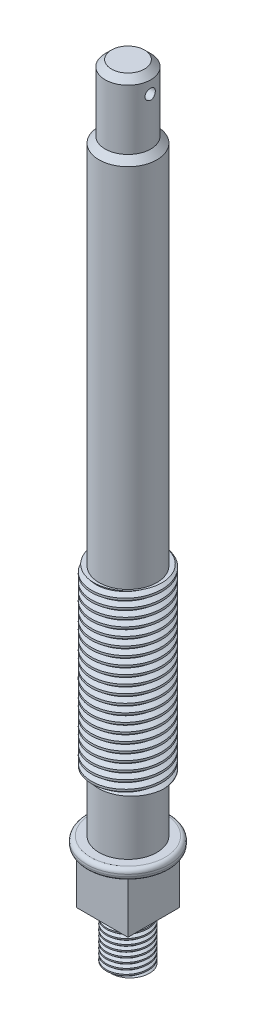
SolidWorks part; units mm, degrees
ref_plane "Front Plane" through (0, 0, 0) normal (0, 0, 1) x (1, 0, 0)
ref_plane "Top Plane" through (0, 0, 0) normal (0, 1, 0) x (1, 0, 0)
ref_plane "Right Plane" through (0, 0, 0) normal (1, 0, 0) x (0, 0, -1)
sketch "Sketch1" plane through (0, 0, 0) normal (0, 0, 1) x (1, 0, 0)
  line L0 (0, -0.1214) -> (0, -30394.4692) construction
  line L1 (0, 0) -> (30394.3478, 0) construction
  line L2 (0, 0) -> (11, 0)
  line L3 (11, 0) -> (11, -32)
  line L4 (11, -32) -> (14, -32)
  line L5 (14, -32) -> (14, -212)
  line L6 (14, -212) -> (17, -212)
  line L7 (17, -212) -> (17, -297)
  line L8 (17, -297) -> (14, -297)
  line L9 (14, -297) -> (14, -325)
  line L10 (14, -325) -> (20, -325)
  line L11 (20, -325) -> (20, -330)
  line L12 (20, -330) -> (10, -330)
  line L13 (10, -330) -> (10, -378)
  line L14 (10, -378) -> (0, -378)
  line L15 (0, -378) -> (0, 0)
  dimension "D1" = 22
  dimension "D2" = 28
  dimension "D3" = 32
  dimension "D4" = 180
  dimension "D5" = 85
  dimension "D6" = 28
  dimension "D7" = 5
  dimension "D8" = 48
  dimension "D9" = 20
  dimension "D10" = 28
  dimension "D11" = 40
  dimension "D12" = 34
  dimension "D13" = 378
revolve "Revolve1" add sketch "Sketch1" angle 360 about L0
sketch "Sketch2" plane through (0, -330, 0) normal (0, -1, 0) x (1, 0, 0)
  line L1 (-12.5, 12.5) -> (12.5, 12.5)
  line L2 (-12.5, 12.5) -> (-12.5, -12.5)
  line L3 (-12.5, -12.5) -> (12.5, -12.5)
  line L4 (12.5, 12.5) -> (12.5, -12.5)
  line L5 (-12.5, 12.5) -> (12.5, -12.5) construction
  line L6 (-12.5, -12.5) -> (12.5, 12.5) construction
  point P0 (0, 0)
  dimension "D1" = 25
extrude "Boss-Extrude1" add sketch "Sketch2" along normal blind 25
thread "Thread1" pitch 4 method cut profile "Thread Profile1" start angle 0, offset 4, length 110, pitch 4, diameter 34
ref_plane "Plane1" through (17, -301, 0) normal (0, 0, -1) x (-1, 0, 0)
sketch "Thread Profile1" plane through (17, -301, 0) normal (0, 0, -1) x (-1, 0, 0)
  line L0 (0, 0) -> (0, 4) construction
  line L1 (0, 0) -> (2.1651, 1.25)
  line L2 (2.1651, 1.25) -> (2.1651, 1.75)
  line L3 (2.1651, 1.75) -> (0, 3)
  line L4 (2.1651, 1.5) -> (0, 1.5) construction
  line L11 (0, 0) -> (0, 3)
  point P2 (0, 0)
  dimension "Pitch" = 4
  dimension "Profile_Angle" = 60
  dimension "Profile_Land" = 0.5
  dimension "Profile_Height" = 2.1651
thread "Thread4" pitch 2.5 method cut profile "Thread Profile6" start angle 0, offset 0, length 0, pitch 2.5, diameter 20
ref_plane "Plane6" through (-10, -355, 0) normal (0, 0, -1) x (1, 0, 0)
sketch "Thread Profile6" plane through (-10, -355, 0) normal (0, 0, -1) x (1, 0, 0)
  line L0 (0, 0) -> (0, 2.5) construction
  line L1 (0, 0) -> (1.3532, 0.7812)
  line L2 (1.3532, 0.7812) -> (1.3532, 1.0937)
  line L3 (1.3532, 1.0937) -> (0, 1.875)
  line L4 (1.3532, 0.9375) -> (0, 0.9375) construction
  line L11 (0, 0) -> (0, 1.875)
  point P2 (0, 0)
  dimension "Pitch" = 2.5
  dimension "Profile_Angle" = 60
  dimension "Profile_Land" = 0.3125
  dimension "Profile_Height" = 1.3532
sketch "Sketch26" plane through (0, 0, 0) normal (1, 0, 0) x (0, 0, -1)
  line L0 (14, -32) -> (-14, -32) construction
  circle A0 centre (0, -9) radius 2.5
  dimension "D2" = 5
  dimension "D1" = 23
extrude "Cut-Extrude1" cut sketch "Sketch26" against normal through all both and the other way through all
fillet "Fillet1" radius 2 2 edges at (-20, -325, 0) (-20, -330, 0)
chamfer "Chamfer1" distance 3 angle 45 2 edges at (-11, 0, 0) (-14, -32, 0)
